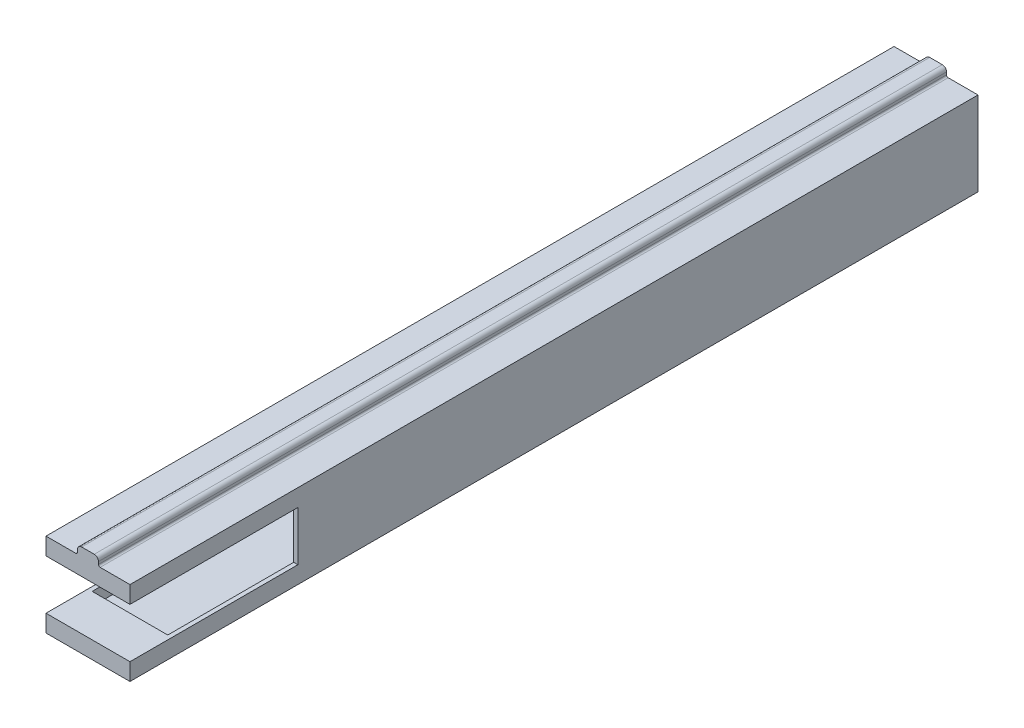
SolidWorks part; units mm, degrees
ref_plane "Front Plane" through (0, 0, 0) normal (0, 0, 1) x (1, 0, 0)
ref_plane "Top Plane" through (0, 0, 0) normal (0, 1, 0) x (1, 0, 0)
ref_plane "Right Plane" through (0, 0, 0) normal (1, 0, 0) x (0, 0, -1)
sketch "Sketch1" plane through (0, 0, 0) normal (0, 0, 1) x (1, 0, 0)
  line L0 (0, 14.5892) -> (0, -5.317) construction
  line L1 (-12.7, -12.7) -> (12.7, -12.7)
  line L2 (12.7, -12.7) -> (12.7, 12.7)
  line L3 (12.7, 12.7) -> (3.175, 12.7)
  line L4 (3.175, 12.7) -> (3.175, 15.24)
  line L5 (3.175, 15.24) -> (-3.175, 15.24)
  line L6 (-12.7, -12.7) -> (-12.7, 12.7)
  line L7 (-3.175, 12.7) -> (-3.175, 15.24)
  line L8 (-12.7, 12.7) -> (-3.175, 12.7)
  circle A0 centre (0, 0) radius 6.35 construction
  circle A1 centre (0, 0) radius 12.7 construction
  circle A2 centre (0, 0) radius 9.525 construction
  circle A3 centre (0, -9.525) radius 1.778
  circle A4 centre (-8.2489, 4.7625) radius 1.778
  circle A5 centre (8.2489, 4.7625) radius 1.778
  circle A6 centre (0, 0) radius 6.35
  point P13 (0, 0)
  point P22 (0, -12.7)
  point P25 (0, 15.24)
  dimension "D1" = 12.7
  dimension "D2" = 25.4
  dimension "D3" = 19.05
  dimension "D4" = 3.556
  dimension "D6" = 9.525
  dimension "D7" = 25.4
  dimension "D8" = 12.7
  dimension "D9" = 12.7
  dimension "D10" = 2.54
  dimension "D5" = 3
extrude "Boss-Extrude1" add sketch "Sketch1" along normal blind 2.54
sketch "Sketch2" plane through (0, 0, 2.54) normal (0, 0, 1) x (1, 0, 0)
  line L0 (-11.43, 11.43) -> (-11.43, -11.43)
  line L1 (-11.43, -11.43) -> (11.43, -11.43)
  line L2 (11.43, -11.43) -> (11.43, 11.43)
  line L3 (11.43, 11.43) -> (-11.43, 11.43)
  line L4 (-12.7, 12.7) -> (-12.7, -12.7) construction
  line L6 (-12.7, -12.7) -> (12.7, -12.7) construction
  line L7 (12.7, -12.7) -> (12.7, 12.7) construction
  line L8 (12.7, 12.7) -> (3.175, 12.7) construction
  line L9 (3.175, 12.7) -> (3.175, 15.24) construction
  line L10 (3.175, 15.24) -> (-3.175, 15.24) construction
  line L11 (-3.175, 15.24) -> (-3.175, 12.7) construction
  line L12 (-3.175, 12.7) -> (-12.7, 12.7) construction
  line L13 (-12.7, -12.7) -> (12.7, -12.7)
  line L14 (12.7, -12.7) -> (12.7, 12.7)
  line L15 (12.7, 12.7) -> (3.175, 12.7)
  line L16 (3.175, 12.7) -> (3.175, 15.24)
  line L17 (3.175, 15.24) -> (-3.175, 15.24)
  line L18 (-3.175, 15.24) -> (-3.175, 12.7)
  line L19 (-3.175, 12.7) -> (-12.7, 12.7)
  line L20 (-12.7, 12.7) -> (-12.7, -12.7)
  dimension "D1" = 22.86
  dimension "D2" = 22.86
  dimension "D3" = 1.27
  dimension "D4" = 1.27
extrude "Boss-Extrude2" add sketch "Sketch2" along normal blind 254
fillet "Fillet1" radius 1.27 2 edges at (3.175, 15.24, 128.27) (-3.175, 15.24, 128.27)
fillet "Fillet2" radius 0.508 2 edges at (3.175, 12.7, 128.27) (-3.175, 12.7, 128.27)
sketch "Sketch3" plane through (0, 11.43, 0) normal (0, -1, 0) x (1, 0, 0)
  line L0 (-11.43, 256.54) -> (11.43, 256.54)
  line L1 (-11.43, 256.54) -> (-11.43, 2.54) construction
  line L5 (-11.43, 256.54) -> (-11.43, 243.84)
  line L7 (-11.43, 243.84) -> (11.43, 243.84)
  line L8 (11.43, 256.54) -> (11.43, 243.84)
  point P6 (0, 0)
  point P8 (0, 0)
  point P9 (-11.43, 243.84)
  dimension "D2" = 12.7
extrude "Boss-Extrude3" add sketch "Sketch3" along normal blind 3.9294
sketch "Sketch4" plane through (0, -11.43, 0) normal (0, 1, 0) x (1, 0, 0)
  line L1 (-11.43, -256.54) -> (11.43, -256.54)
  line L2 (-11.43, -256.54) -> (-11.43, -243.84)
  line L3 (-11.43, -243.84) -> (11.43, -243.84)
  line L4 (11.43, -256.54) -> (11.43, -243.84)
  line L7 (-11.43, -256.54) -> (11.43, -256.54) construction
  line L8 (-11.43, -256.54) -> (-11.43, -2.54) construction
  line L9 (11.43, -256.54) -> (11.43, -2.54) construction
  dimension "D1" = 12.7
  dimension "D2" = 22.86
extrude "Boss-Extrude4" add sketch "Sketch4" along normal blind 3.9294
sketch "Sketch5" plane through (0, 0, 256.54) normal (0, 0, 1) x (1, 0, 0)
  line L0 (-12.7, 12.7) -> (-12.7, -12.7) construction
  line L1 (-12.7, 7.5006) -> (12.7, 7.5006)
  line L2 (-12.7, 7.5006) -> (-12.7, -7.5006)
  line L3 (-12.7, -7.5006) -> (12.7, -7.5006)
  line L4 (12.7, 7.5006) -> (12.7, -7.5006)
  line L5 (12.7, -12.7) -> (12.7, 12.7) construction
extrude "Cut-Extrude1" cut sketch "Sketch5" against normal blind 50.8
